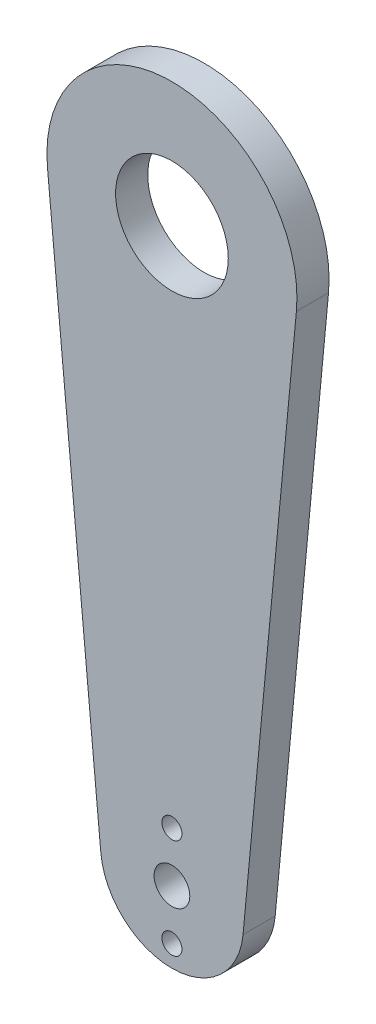
SolidWorks part; units mm, degrees
ref_plane "Front Plane" through (0, 0, 0) normal (0, 0, 1) x (1, 0, 0)
ref_plane "Top Plane" through (0, 0, 0) normal (0, 1, 0) x (1, 0, 0)
ref_plane "Right Plane" through (0, 0, 0) normal (1, 0, 0) x (0, 0, -1)
ref_axis "X Axis" through (-88.99, 0, 0) along (1, 0, 0)
ref_axis "Y Axiz" through (0, 0, 55) along (0, 0, -1)
ref_axis "Z Axis" through (0, 55, 0) along (0, -1, 0)
sketch "Sketch1" plane through (0, 0, 0) normal (0, 0, 1) x (1, 0, 0)
  line L1 (-9.956, -0.9375) -> (-17.4229, 78.3594)
  line L3 (0, -7) -> (0, 7) construction
  line L4 (17.4229, 78.3594) -> (9.956, -0.9375)
  line L5 (0, 0) -> (0, 80) construction
  arc A1 (-9.956, -0.9375) -> (9.956, -0.9375) centre (0, 0) ccw
  circle A2 centre (0, 80) radius 7.8875
  arc A3 (17.4229, 78.3594) -> (-17.4229, 78.3594) centre (0, 80) ccw
  circle A5 centre (0, 0) radius 2.5
  circle A6 centre (0, 7) radius 1.4
  circle A7 centre (0, -7) radius 1.4
  point P7 (0, 0)
  dimension "D1" = 5
  dimension "D3" = 20
  dimension "D4" = 15.775
  dimension "D5" = 35
  dimension "D2" = 2.8
  dimension "D6" = 80
  dimension "D7" = 7
extrude "Boss-Extrude1" add sketch "Sketch1" along normal blind 4.5
